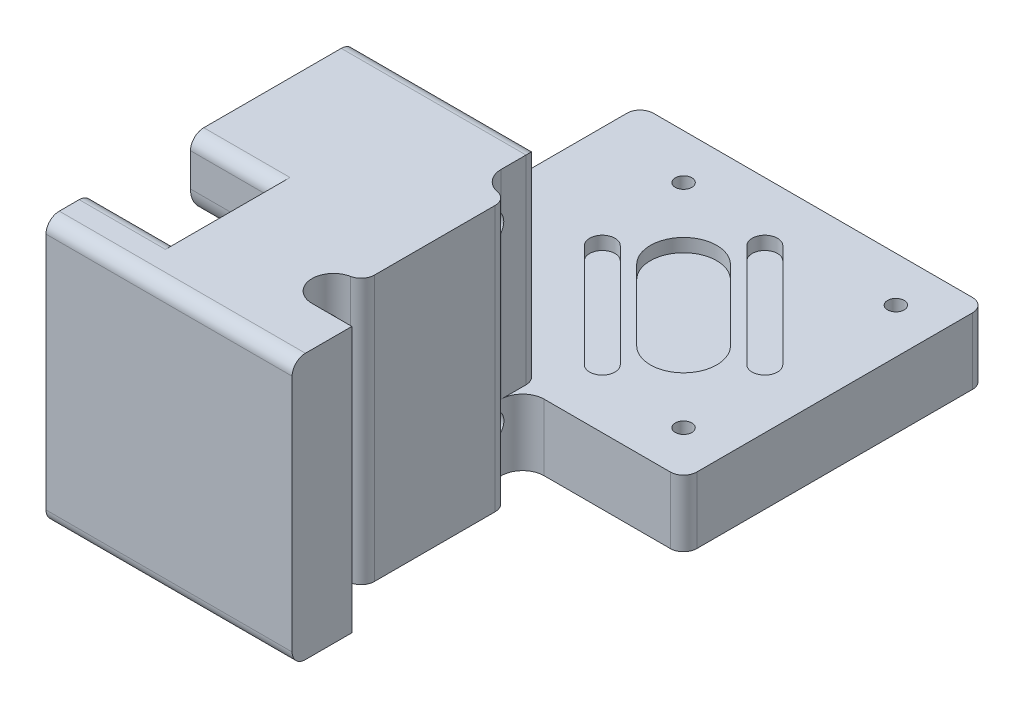
SolidWorks part; units mm, degrees
material "AISI 1045 Steel, cold drawn"
ref_plane "Front Plane" through (0, 0, 0) normal (0, 0, 1) x (1, 0, 0)
ref_plane "Top Plane" through (0, 0, 0) normal (0, 1, 0) x (1, 0, 0)
ref_plane "Right Plane" through (0, 0, 0) normal (1, 0, 0) x (0, 0, -1)
sketch "Sketch1" plane through (0, 0, 0) normal (0, 1, 0) x (1, 0, 0)
  line L0 (-211.9, -221.9) -> (-183.9, -221.9) construction
  line L1 (250, -250) -> (-250, -250)
  line L2 (250, -250) -> (250, 250)
  line L3 (250, 250) -> (-250, 250)
  line L4 (-250, -250) -> (-250, 250)
  line L5 (250, -250) -> (-250, 250) construction
  line L6 (250, 250) -> (-250, -250) construction
  line L7 (-250, -250) -> (-211.9, -250)
  line L8 (-250, -250) -> (-250, -211.9)
  line L9 (-250, -211.9) -> (-211.9, -211.9)
  line L10 (-211.9, -250) -> (-211.9, -211.9)
  line L11 (-211.9, -238.9) -> (-183.9, -238.9)
  line L12 (-211.9, -238.9) -> (-211.9, -204.9)
  line L13 (-211.9, -204.9) -> (-183.9, -204.9)
  line L14 (-183.9, -238.9) -> (-183.9, -204.9)
  line L16 (152.5, 152.5) -> (-152.5, 152.5)
  line L17 (152.5, 152.5) -> (152.5, -152.5)
  line L18 (152.5, -152.5) -> (-152.5, -152.5)
  line L19 (-152.5, 152.5) -> (-152.5, -152.5)
  line L20 (152.5, 152.5) -> (-152.5, -152.5) construction
  line L21 (152.5, -152.5) -> (-152.5, 152.5) construction
  point P0 (0, 0)
  point P15 (-158.3, -233)
  point P16 (-188.9, -188.9)
  point P17 (0, 0)
  point P22 (-181.1218, -181.1218)
  dimension "D1" = 500
  dimension "D2" = 38.1
  dimension "D3" = 28
  dimension "D4" = 17
  dimension "D5" = 20
  dimension "D6" = 91.7
  dimension "D7" = 17
  dimension "D8" = 305
  dimension "D9" = 5
  dimension "D10" = 11
ref_plane "Plane1" through (-188.9, 0, 188.9) normal (-0.7071, 0, 0.7071) x (0.7071, 0, 0.7071)
sketch "Sketch3" plane through (-188.9, 0, 188.9) normal (-0.7071, 0, 0.7071) x (0.7071, 0, 0.7071)
  line L0 (-8.6603, -5) -> (8.6603, -5) construction
  line L1 (0, 0) -> (0, -5) construction
  line L2 (-8.6603, -5) -> (0, 0) construction
  line L3 (-6.7451, -6.607) -> (-8.6603, -5) construction
  line L4 (-6.7451, -6.607) -> (6.7451, -6.607)
  line L5 (-6.7451, -6.607) -> (-6.7451, -16.607)
  line L6 (-6.7451, -16.607) -> (6.7451, -16.607)
  line L7 (6.7451, -6.607) -> (6.7451, -16.607)
  line L8 (10.5754, -16.607) -> (13.5754, -16.607)
  line L9 (-10.5754, -6.607) -> (-13.5754, -6.607)
  line L10 (-10.5754, -6.607) -> (-10.5754, -16.607)
  line L11 (-10.5754, -16.607) -> (-13.5754, -16.607)
  line L12 (-13.5754, -6.607) -> (-13.5754, -16.607)
  line L13 (13.5754, -6.607) -> (13.5754, -16.607)
  line L14 (10.5754, -6.607) -> (13.5754, -6.607)
  line L15 (10.5754, -6.607) -> (10.5754, -16.607)
  circle A0 centre (0, 0) radius 7.5
  circle A1 centre (-8.6603, -5) radius 2.5
  circle A2 centre (8.6603, -5) radius 2.5
  point P20 (-10.5754, -3.393)
  dimension "D1" = 15
  dimension "D2" = 5
  dimension "D3" = 30
  dimension "D4" = 10
  dimension "D5" = 40
  dimension "D6" = 3
extrude "Boss-Extrude1" add sketch "Sketch3" against normal blind 22 contours L9 L12 L11 L10 | L7 L4 L5 L6 | L14 L15 L8 L13 | L4 A0
sketch "Sketch4" plane through (-188.9, 0, 188.9) normal (-0.7071, 0, 0.7071) x (0.7071, 0, 0.7071)
  line L1 (-13.5754, -16.607) -> (13.5754, -16.607)
  line L2 (-13.5754, -16.607) -> (-13.5754, -6.607)
  line L3 (-13.5754, -6.607) -> (13.5754, -6.607)
  line L4 (13.5754, -16.607) -> (13.5754, -6.607)
extrude "Boss-Extrude2" add sketch "Sketch4" along normal blind 3
sketch "Sketch5" plane through (-173.3437, 0, 173.3437) normal (0.7071, 0, -0.7071) x (-0.7071, 0, -0.7071)
  line L1 (-13.5754, -16.607) -> (13.5754, -16.607)
  line L2 (-13.5754, -16.607) -> (-13.5754, -6.607)
  line L3 (-13.5754, -6.607) -> (13.5754, -6.607)
  line L4 (13.5754, -16.607) -> (13.5754, -6.607)
extrude "Boss-Extrude3" add sketch "Sketch5" along normal blind 3
sketch "Sketch7" plane through (0, -6.607, 0) normal (0, 1, 0) x (1, 0, 0)
  line L0 (-188.9, -238.9) -> (-183.9, -238.9)
  line L1 (-211.9, -238.9) -> (-183.9, -238.9) construction
  line L2 (-183.9, -238.9) -> (-183.9, -203.9)
  line L4 (-188.9, -238.9) -> (-188.9, -245.9)
  line L5 (-188.9, -245.9) -> (-146.8, -245.9)
  line L13 (-184.7015, -203.9) -> (-161.6231, -180.8216)
  line L15 (-183.9, -203.9) -> (-200.6206, -203.9)
  line L33 (-200.6206, -203.9) -> (-200.6206, -181.4221)
  line L34 (-200.6206, -181.4221) -> (-178.1426, -203.9)
  line L35 (-211.9, -204.9) -> (-183.9, -204.9) construction
  line L37 (-151.8, -239.88) -> (-164.8, -239.88) construction
  line L38 (-151.8, -239.88) -> (-151.8, -226.12)
  line L39 (-151.8, -226.12) -> (-164.8, -226.12)
  line L40 (-164.8, -239.88) -> (-164.8, -226.12)
  line L41 (-151.8, -239.88) -> (-164.8, -226.12) construction
  line L42 (-151.8, -226.12) -> (-164.8, -239.88) construction
  line L44 (-146.8, -161.6231) -> (-146.8, -245.9)
  line L45 (-164.8, -239.88) -> (-164.8, -240.9)
  line L46 (-164.8, -240.9) -> (-151.8, -240.9)
  line L47 (-151.8, -240.9) -> (-151.8, -239.88)
  line L48 (-181.4221, -200.6206) -> (-200.6206, -181.4221) construction
  line L49 (-181.4221, -200.6206) -> (-161.6231, -180.8216) construction
  line L50 (-161.6231, -180.8216) -> (-180.8216, -161.6231)
  line L51 (-180.8216, -161.6231) -> (-146.8, -161.6231)
  point P17 (-158.3, -233)
  dimension "D3" = 5
  dimension "D4" = 13.76
  dimension "D1" = 5
  dimension "D2" = 1
  dimension "D5" = 13
  dimension "D6" = 7
  dimension "D7" = 5
extrude "Boss-Extrude4" add sketch "Sketch7" against normal up to surface (10 mm away) up to face at (-181.1218, -16.607, 181.1218)
sketch "Sketch13" plane through (0, -6.607, 0) normal (0, 1, 0) x (1, 0, 0)
  line L2 (-181.4221, -196.3779) -> (-181.4221, -203.9) construction
  line L3 (-200.6206, -203.9) -> (-203.9, -203.9)
  line L4 (-200.6206, -203.9) -> (-200.6206, -181.4221)
  line L5 (-180.8216, -161.6231) -> (-200.6206, -181.4221)
  line L7 (-203.9, -203.9) -> (-203.9, -158.3437)
  line L8 (-183.9, -203.9) -> (-200.6206, -203.9) construction
  line L9 (-196.3779, -181.4221) -> (-203.9, -181.4221) construction
  line L10 (-180.8216, -165.8657) -> (-180.8216, -158.3437) construction
  line L11 (-180.8216, -161.6231) -> (-146.8, -161.6231)
  line L12 (-146.8, -161.6231) -> (-146.8, -158.3437)
  line L13 (-146.8, -158.3437) -> (-203.9, -158.3437)
extrude "Boss-Extrude5" add sketch "Sketch13" against normal up to surface (10 mm away) up to face at (-180.1403, -16.607, 209.1187)
sketch "Sketch15" plane through (0, -6.607, 0) normal (0, 1, 0) x (1, 0, 0)
  line L0 (-180.8216, -165.8657) -> (-178.1132, -168.5741) construction
  line L5 (-168.5741, -178.1132) -> (-165.8657, -180.8216) construction
  line L10 (-193.6695, -184.1305) -> (-196.3779, -181.4221) construction
  line L11 (-181.4221, -196.3779) -> (-184.1305, -193.6695) construction
  circle A8 centre (-179.4674, -167.2199) radius 1.9151
  circle A9 centre (-167.2199, -179.4674) radius 1.9151
  circle A10 centre (-195.0237, -182.7763) radius 1.9151
  circle A11 centre (-182.7763, -195.0237) radius 1.9151
extrude "Cut-Extrude4" cut sketch "Sketch15" against normal through all
sketch "Sketch18" plane through (0, -6.607, 0) normal (0, 1, 0) x (1, 0, 0)
  line L0 (-183.9, -203.9) -> (-146.8, -203.9)
  line L1 (-151.8, -226.12) -> (-164.8, -226.12) construction
  line L2 (-164.8, -226.12) -> (-164.8, -240.9) construction
  line L3 (-164.8, -240.9) -> (-151.8, -240.9) construction
  line L4 (-151.8, -240.9) -> (-151.8, -226.12) construction
  line L5 (-151.8, -226.12) -> (-164.8, -226.12)
  line L6 (-164.8, -226.12) -> (-164.8, -240.9)
  line L7 (-164.8, -240.9) -> (-151.8, -240.9)
  line L8 (-146.8, -245.9) -> (-146.8, -158.3437)
  line L9 (-146.8, -158.3437) -> (-203.9, -158.3437)
  line L10 (-203.9, -158.3437) -> (-203.9, -203.9)
  line L11 (-203.9, -203.9) -> (-183.9, -203.9)
  line L12 (-183.9, -203.9) -> (-183.9, -238.9)
  line L13 (-183.9, -238.9) -> (-188.9, -238.9)
  line L14 (-188.9, -238.9) -> (-188.9, -245.9)
  line L15 (-188.9, -245.9) -> (-146.8, -245.9)
  line L16 (-146.8, -245.9) -> (-146.8, -203.9)
  line L20 (-183.9, -203.9) -> (-183.9, -238.9)
  line L21 (-183.9, -238.9) -> (-188.9, -238.9)
  line L22 (-188.9, -238.9) -> (-188.9, -245.9)
  line L23 (-188.9, -245.9) -> (-146.8, -245.9)
  line L24 (-151.8, -240.9) -> (-151.8, -226.12)
  dimension "D1" = 0
extrude "Boss-Extrude6" add sketch "Sketch18" along normal blind 30
hole_wizard "M4 Clearance Hole1" positions "Sketch19" profile "Sketch21" hole size "M4" standard "ANSI Metric" end condition through all
sketch "Sketch19" plane through (-146.8, 0, 0) normal (1, 0, 0) x (0, 0, -1)
  line L1 (-234.9, 16.393) -> (-208.9, 16.393)
  line L2 (-234.9, 16.393) -> (-234.9, -9.607)
  line L3 (-234.9, -9.607) -> (-208.9, -9.607)
  line L4 (-208.9, 16.393) -> (-208.9, -9.607)
  line L6 (-245.9, 23.393) -> (-245.9, -16.607) construction
  line L7 (-238.9, -16.607) -> (-238.9, 23.393) construction
  point P2 (-208.9, -9.607)
  point P124 (-208.9, 16.393)
  point P146 (-245.9, 3.393)
  point P147 (-234.9, 3.393)
  dimension "D1" = 26
  dimension "D2" = 26
  dimension "D3" = 4
sketch "Sketch21" plane through (-146.8, 16.393, 208.9) normal (0, 1, 0) x (0, 0, -1)
  line L0 (0, 0) -> (0, 57.1)
  line L1 (0, 57.1) -> (2.15, 57.1)
  line L2 (2.15, 57.1) -> (2.15, 0)
  line L5 (2.15, 0) -> (0, 0)
  line L11 (0, -6.35) -> (0, 107.95) construction
  dimension "Thru Hole Dia." = 4.3
  dimension "Thru Hole Depth" = 57.1
sketch "Sketch22" plane through (-146.8, 0, 0) normal (1, 0, 0) x (0, 0, -1)
  line L6 (-245.9, 23.393) -> (-245.9, -16.607)
  line L7 (-245.9, -16.607) -> (-158.3437, -16.607)
  line L8 (-158.3437, -16.607) -> (-158.3437, -6.607)
  line L9 (-158.3437, -6.607) -> (-203.9, -6.607)
  line L10 (-203.9, -6.607) -> (-203.9, 23.393)
  line L11 (-203.9, 23.393) -> (-245.9, 23.393)
  line L12 (-245.9, 23.393) -> (-245.9, -16.607)
  line L13 (-245.9, -16.607) -> (-158.3437, -16.607)
  line L14 (-158.3437, -16.607) -> (-158.3437, -6.607)
  line L15 (-158.3437, -6.607) -> (-203.9, -6.607)
  line L16 (-203.9, -6.607) -> (-203.9, 23.393)
  line L17 (-203.9, 23.393) -> (-245.9, 23.393)
  dimension "D1" = 0
extrude "Cut-Extrude7" cut sketch "Sketch22" against normal blind 5
sketch "Sketch17" plane through (0, -6.607, 0) normal (0, 1, 0) x (1, 0, 0)
  line L0 (-185.8914, -176.3523) -> (-176.3523, -185.8914) construction
  line L1 (-178.1132, -168.5741) -> (-193.6695, -184.1305) construction
  line L2 (-168.5741, -178.1132) -> (-184.1305, -193.6695) construction
  line L3 (-186.4251, -186.4251) -> (-175.8185, -175.8185) construction
  line L4 (-189.9607, -182.8896) -> (-179.3541, -172.283)
  line L5 (-182.8896, -189.9607) -> (-172.283, -179.3541)
  arc A1 (-189.9607, -182.8896) -> (-182.8896, -189.9607) centre (-186.4251, -186.4251) ccw
  arc A2 (-172.283, -179.3541) -> (-179.3541, -172.283) centre (-175.8185, -175.8185) ccw
  point P8 (-181.1218, -181.1218)
  dimension "D1" = 5
  dimension "D2" = 15
extrude "Cut-Extrude6" cut sketch "Sketch17" against normal blind 2
hole_wizard "Tap Drill for M3x0.5 Tap1" positions "Sketch25" profile "Sketch26" hole size "M3x0.5" standard "ANSI Metric" end condition through all
sketch "Sketch25" plane through (0, -6.607, 0) normal (0, 1, 0) x (1, 0, 0)
  line L1 (-197.1218, -165.1218) -> (-165.1218, -165.1218)
  line L2 (-197.1218, -165.1218) -> (-197.1218, -197.1218)
  line L3 (-197.1218, -197.1218) -> (-165.1218, -197.1218)
  line L4 (-165.1218, -165.1218) -> (-165.1218, -197.1218)
  line L6 (-197.1218, -165.1218) -> (-165.1218, -197.1218) construction
  line L7 (-189.9607, -189.9607) -> (-172.283, -172.283) construction
  arc A2 (-189.9607, -182.8896) -> (-182.8896, -189.9607) centre (-186.4251, -186.4251) ccw construction
  arc A3 (-172.283, -179.3541) -> (-179.3541, -172.283) centre (-175.8185, -175.8185) ccw construction
  point P1 (-197.1218, -165.1218)
  point P2 (-165.1218, -197.1218)
  point P59 (-197.1218, -197.1218)
  point P60 (-165.1218, -165.1218)
  point P88 (-181.1218, -181.1218)
  point P89 (-181.1218, -181.1218)
  dimension "D1" = 32
sketch "Sketch26" plane through (-197.1218, -6.607, 165.1218) normal (1, 0, 0) x (0, 0, 1)
  line L0 (0, 0) -> (0, 10)
  line L1 (0, 10) -> (1.25, 10)
  line L2 (1.25, 10) -> (1.25, 0)
  line L5 (1.25, 0) -> (0, 0)
  line L11 (0, -6.35) -> (0, 107.95) construction
  dimension "Thru Hole Dia." = 2.5
  dimension "Thru Hole Depth" = 10
sketch "Sketch43" plane through (0, 0, 203.9) normal (0, 0, -1) x (-1, 0, 0)
  line L4 (151.8, 23.393) -> (151.8, -6.607)
  line L5 (151.8, -6.607) -> (183.9, -6.607)
  line L6 (183.9, -6.607) -> (183.9, 23.393)
  line L7 (183.9, 23.393) -> (151.8, 23.393)
  line L8 (151.8, 23.393) -> (151.8, -6.607)
  line L9 (151.8, -6.607) -> (183.9, -6.607)
  line L10 (183.9, -6.607) -> (183.9, 23.393)
  line L11 (183.9, 23.393) -> (151.8, 23.393)
  dimension "D1" = 0
extrude "Boss-Extrude9" add sketch "Sketch43" along normal blind 2.5
sketch "Sketch27" plane through (-151.8, 0, 0) normal (1, 0, 0) x (0, 0, -1)
  line L0 (-226.12, -16.607) -> (-226.12, 23.393) construction
  line L1 (-226.12, 12.393) -> (-203.4, 12.393)
  line L2 (-226.12, 12.393) -> (-226.12, 0.393)
  line L3 (-226.12, 0.393) -> (-203.4, 0.393)
  line L4 (-203.4, 12.393) -> (-203.4, 0.393)
  line L6 (-201.4, 23.393) -> (-201.4, -6.607) construction
  circle A0 centre (-208.9, 16.393) radius 2.15 construction
  dimension "D3" = 4
  dimension "D1" = 12
  dimension "D2" = 2
extrude "Cut-Extrude9" cut sketch "Sketch27" against normal up to surface (13 mm away) up to face at (-164.8, 3.393, 233.51)
fillet "Fillet1" radius 2 2 edges at (-158.3, 0.393, 203.4) (-158.3, 12.393, 203.4)
fillet "Fillet2" radius 4 2 edges at (-158.3, 0.393, 226.12) (-158.3, 12.393, 226.12)
hole_wizard "CBORE for M4 SHCS1" positions "Sketch29" profile "Sketch30" counterbore size "M4" standard "ANSI Metric" end condition through all
sketch "Sketch29" plane through (-164.8, 0, 0) normal (1, 0, 0) x (0, 0, -1)
  point P0 (-234.9, 16.393)
  point P3 (-234.9, -9.607)
sketch "Sketch30" plane through (-164.8, 16.393, 234.9) normal (0, 1, 0) x (0, 0, -1)
  line L0 (0, 0) -> (0, 39.1)
  line L1 (0, 39.1) -> (2.15, 39.1)
  line L3 (2.15, 39.1) -> (2.15, 5)
  line L4 (2.15, 5) -> (4, 5)
  line L5 (4, 5) -> (4, 0)
  line L7 (4, 0) -> (0, 0)
  line L11 (0, -6.35) -> (0, 107.95) construction
  dimension "Thru Hole Dia." = 4.3
  dimension "Thru Hole Depth" = 39.1
  dimension "C'Bore Dia." = 8
  dimension "C'Bore Depth" = 5
sketch "Sketch31" plane through (0, 0, 245.9) normal (0, 0, 1) x (1, 0, 0)
  line L4 (-188.9, -16.607) -> (-151.8, -16.607)
  line L5 (-151.8, -16.607) -> (-151.8, 23.393)
  line L6 (-151.8, 23.393) -> (-188.9, 23.393)
  line L7 (-188.9, 23.393) -> (-188.9, -16.607)
  line L8 (-188.9, -16.607) -> (-151.8, -16.607)
  line L9 (-151.8, -16.607) -> (-151.8, 23.393)
  line L10 (-151.8, 23.393) -> (-188.9, 23.393)
  line L11 (-188.9, 23.393) -> (-188.9, -16.607)
  dimension "D1" = 0
extrude "Boss-Extrude8" add sketch "Sketch31" along normal blind 2
hole_wizard "Tap Drill for M3x0.5 Tap2" positions "Sketch34" profile "Sketch35" hole size "M3x0.5" standard "ANSI Metric"
sketch "Sketch34" plane through (-151.8, 0, 0) normal (1, 0, 0) x (0, 0, -1)
  line L1 (-234.9, 16.393) -> (-244.4, 16.393)
  line L2 (-234.9, 16.393) -> (-234.9, -9.607)
  line L3 (-234.9, -9.607) -> (-244.4, -9.607)
  line L4 (-244.4, 16.393) -> (-244.4, -9.607)
  line L6 (-240.9, 3.393) -> (-247.9, 3.393) construction
  line L7 (-240.9, -16.607) -> (-240.9, 23.393) construction
  line L8 (-247.9, -16.607) -> (-247.9, 23.393) construction
  point P2 (-244.4, -9.607)
  point P114 (-244.4, 16.393)
  point P129 (-244.4, 3.393)
sketch "Sketch35" plane through (-151.8, 16.393, 244.4) normal (0, 1, 0) x (0, 0, -1)
  line L0 (0, 0) -> (0, 8.7511)
  line L1 (0, 8.7511) -> (1.25, 8)
  line L2 (1.25, 8) -> (1.25, 0)
  line L5 (1.25, 0) -> (0, 0)
  line L10 (0, 8.7511) -> (-1.25, 8) construction
  line L11 (0, -6.35) -> (0, 107.95) construction
  dimension "Hole Dia." = 2.5
  dimension "Hole Depth" = 8
  dimension "Drill Angle" = 118
fillet "Fillet4" radius 2 10 edges at (-203.9, -11.607, 203.9) (-203.9, -11.607, 158.3437) (-151.8, -11.607, 158.3437) (-158.3, -16.607, 240.9) (-158.3, 23.393, 240.9) (-158.3, 23.393, 226.12) (-158.3, -16.607, 226.12) (-170.35, -16.607, 247.9) (-170.35, 23.393, 247.9) (-167.85, 23.393, 201.4)
sketch "Sketch36" plane through (0, 23.393, 0) normal (0, 1, 0) x (1, 0, 0)
  line L6 (-183.9, -238.9) -> (-188.9, -238.9) construction
  line L7 (-183.9, -203.4) -> (-183.9, -238.9) construction
  line L10 (-183.9, -203.9) -> (-201.9, -203.9) construction
  line L12 (-182.9, -232.4) -> (-183.9, -232.4)
  line L13 (-183.9, -232.4) -> (-183.9, -238.9)
  line L14 (-183.9, -238.9) -> (-182.9, -238.9)
  line L20 (-183.9, -210.4) -> (-183.9, -201.4)
  line L21 (-182.9, -210.4) -> (-183.9, -210.4)
  line L22 (-179.65, -207.15) -> (-179.65, -203.4)
  line L23 (-183.9, -201.4) -> (-151.8, -201.4) construction
  line L24 (-177.65, -201.4) -> (-183.9, -201.4)
  line L25 (-183.9, -203.4) -> (-183.9, -238.9) construction
  line L26 (-151.8, -201.4) -> (-183.9, -201.4) construction
  arc A1 (-182.9, -238.9) -> (-182.9, -232.4) centre (-182.9, -235.65) ccw
  arc A4 (-179.65, -207.15) -> (-182.9, -210.4) centre (-182.9, -207.15) cw
  arc A5 (-179.65, -203.4) -> (-177.65, -201.4) centre (-177.65, -203.4) cw
  dimension "D1" = 3.25
  dimension "D2" = 3.25
  dimension "D4" = 2
  dimension "D3" = 1
extrude "Cut-Extrude10" cut sketch "Sketch36" against normal up to surface (30 mm away) up to face at (-197.1218, -6.607, 166.3718)
sketch "Sketch44" plane through (0, -6.607, 0) normal (0, 1, 0) x (1, 0, 0)
  line L0 (-183.9, -210.4) -> (-182.9, -210.4) construction
  line L1 (-183.9, -210.4) -> (-183.9, -203.9) construction
  line L2 (-183.9, -210.4) -> (-182.9, -210.4)
  line L3 (-182.9, -232.4) -> (-183.9, -232.4)
  line L4 (-183.9, -232.4) -> (-183.9, -238.9)
  line L5 (-183.9, -238.9) -> (-182.9, -238.9)
  line L6 (-182.9, -232.4) -> (-183.9, -232.4)
  line L7 (-183.9, -232.4) -> (-183.9, -238.9)
  line L8 (-183.9, -238.9) -> (-182.9, -238.9)
  line L9 (-183.9, -210.4) -> (-183.9, -203.9)
  line L13 (-183.9, -203.9) -> (-182.9, -203.9)
  arc A0 (-182.9, -210.4) -> (-179.65, -207.15) centre (-182.9, -207.15) ccw construction
  arc A1 (-182.9, -238.9) -> (-182.9, -232.4) centre (-182.9, -235.65) ccw
  arc A2 (-182.9, -238.9) -> (-182.9, -232.4) centre (-182.9, -235.65) ccw
  arc A3 (-182.9, -210.4) -> (-182.9, -203.9) centre (-182.9, -207.15) ccw
  dimension "D1" = 0
extrude "Cut-Extrude12" cut sketch "Sketch44" against normal up to surface (10 mm away) up to face at (-197.1218, -16.607, 166.3718)
fillet "Fillet5" radius 2 2 edges at (-183.9, 3.393, 232.4) (-183.9, 3.393, 210.4)
hole_wizard "M5 Clearance Hole1" positions "Sketch40" profile "Sketch42" hole size "M5" standard "ANSI Metric" end condition up to next
sketch "Sketch40" plane through (0, 0, 201.4) normal (0, 0, -1) x (-1, 0, 0)
  line L0 (151.8, 6.393) -> (157.85, 6.393) construction
  line L3 (164.8, 12.393) -> (151.8, 12.393) construction
  line L4 (151.8, 21.393) -> (151.8, -6.607) construction
  point P0 (157.85, 6.393)
  dimension "D1" = 6.05
  dimension "D2" = 6
sketch "Sketch42" plane through (-157.85, 6.393, 201.4) normal (1, 0, 0) x (0, 1, 0)
  line L0 (0, 0) -> (0, 2)
  line L1 (0, 2) -> (2.65, 2)
  line L2 (2.65, 2) -> (2.65, 0)
  line L5 (2.65, 0) -> (0, 0)
  line L11 (0, -6.35) -> (0, 107.95) construction
  dimension "Thru Hole Dia." = 5.3
  dimension "Thru Hole Depth" = 2
sketch "Sketch45" plane through (0, -16.607, 0) normal (0, -1, 0) x (1, 0, 0)
  line L0 (-180.8216, 165.8657) -> (-196.3779, 181.4221) construction
  line L1 (-178.1132, 168.5741) -> (-193.6695, 184.1305) construction
  line L2 (-165.8657, 180.8216) -> (-181.4221, 196.3779)
  line L3 (-184.1305, 193.6695) -> (-168.5741, 178.1132)
  line L4 (-165.8657, 180.8216) -> (-181.4221, 196.3779)
  line L5 (-184.1305, 193.6695) -> (-168.5741, 178.1132)
  line L6 (-180.8216, 165.8657) -> (-196.3779, 181.4221)
  line L7 (-178.1132, 168.5741) -> (-193.6695, 184.1305)
  arc A0 (-180.8216, 165.8657) -> (-178.1132, 168.5741) centre (-179.4674, 167.2199) ccw construction
  arc A1 (-193.6695, 184.1305) -> (-196.3779, 181.4221) centre (-195.0237, 182.7763) ccw construction
  arc A2 (-168.5741, 178.1132) -> (-165.8657, 180.8216) centre (-167.2199, 179.4674) ccw
  arc A3 (-181.4221, 196.3779) -> (-184.1305, 193.6695) centre (-182.7763, 195.0237) ccw
  arc A4 (-168.5741, 178.1132) -> (-165.8657, 180.8216) centre (-167.2199, 179.4674) ccw
  arc A5 (-181.4221, 196.3779) -> (-184.1305, 193.6695) centre (-182.7763, 195.0237) ccw
  arc A6 (-180.8216, 165.8657) -> (-178.1132, 168.5741) centre (-179.4674, 167.2199) ccw
  arc A7 (-193.6695, 184.1305) -> (-196.3779, 181.4221) centre (-195.0237, 182.7763) ccw
  dimension "D1" = 0
extrude "Boss-Extrude10" add sketch "Sketch45" against normal up to surface (8 mm away) up to face at (-181.1218, -8.607, 181.1218)
mirror "Mirror1" about plane through (-151.8, 0, 0) normal (1, 0, 0) of bodies 156
delete or keep bodies "Body-Delete/Keep 1" type delete bodies bodies 156
